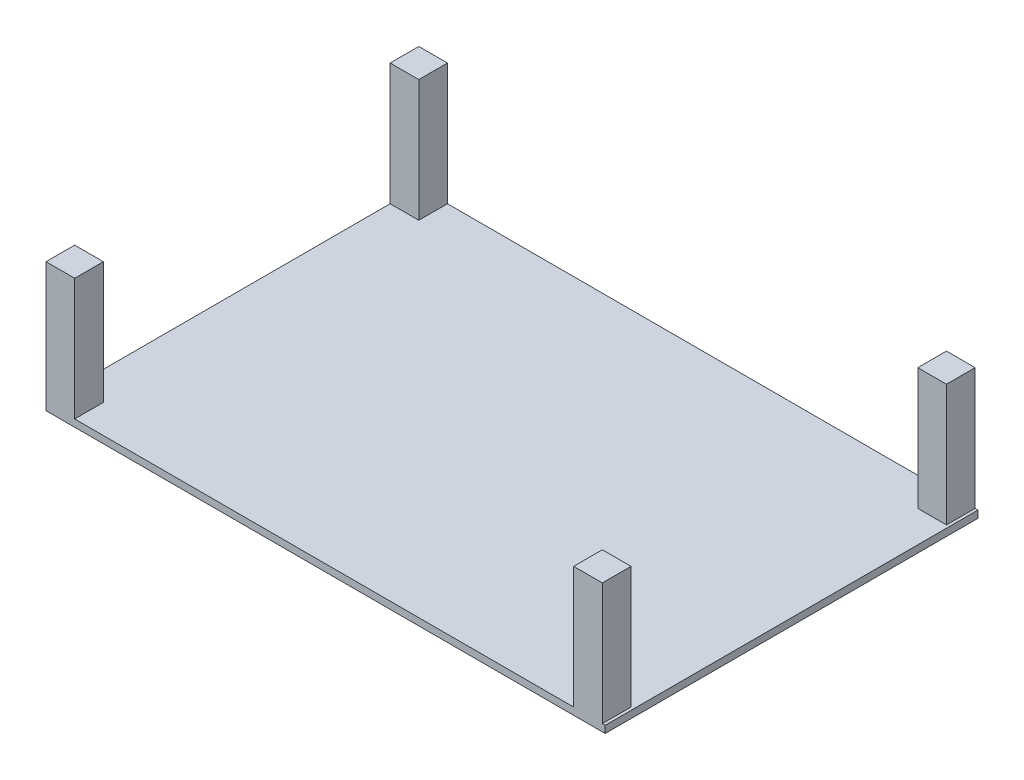
SolidWorks part; units mm, degrees
ref_plane "Front Plane" through (0, 0, 0) normal (0, 0, 1) x (1, 0, 0)
ref_plane "Top Plane" through (0, 0, 0) normal (0, 1, 0) x (1, 0, 0)
ref_plane "Right Plane" through (0, 0, 0) normal (1, 0, 0) x (0, 0, -1)
sketch "Sketch2" plane through (0, 0, 0) normal (0, 1, 0) x (1, 0, 0)
  line L1 (-123.825, -82.55) -> (123.825, -82.55)
  line L2 (-123.825, -82.55) -> (-123.825, 82.55)
  line L3 (-123.825, 82.55) -> (123.825, 82.55)
  line L4 (123.825, -82.55) -> (123.825, 82.55)
  line L5 (-123.825, -82.55) -> (123.825, 82.55) construction
  line L6 (-123.825, 82.55) -> (123.825, -82.55) construction
  point P0 (0, 0)
  dimension "D1" = 165.1
  dimension "D2" = 247.65
extrude "Boss-Extrude1" add sketch "Sketch2" along normal blind 3.175
sketch "Sketch3" plane through (0, 3.175, 0) normal (0, 1, 0) x (1, 0, 0)
  line L1 (-123.825, -82.55) -> (-111.125, -82.55)
  line L2 (-123.825, -82.55) -> (-123.825, -69.85)
  line L3 (-123.825, -69.85) -> (-111.125, -69.85)
  line L4 (-111.125, -82.55) -> (-111.125, -69.85)
  dimension "D1" = 12.7
  dimension "D2" = 12.7
extrude "Boss-Extrude2" add sketch "Sketch3" along normal blind 53.975
pattern_linear "LPattern1" count 2 spacing 152.4 along (0, 0, -1) count 2 spacing 233.68 along (1, 0, 0) of "Boss-Extrude2"
